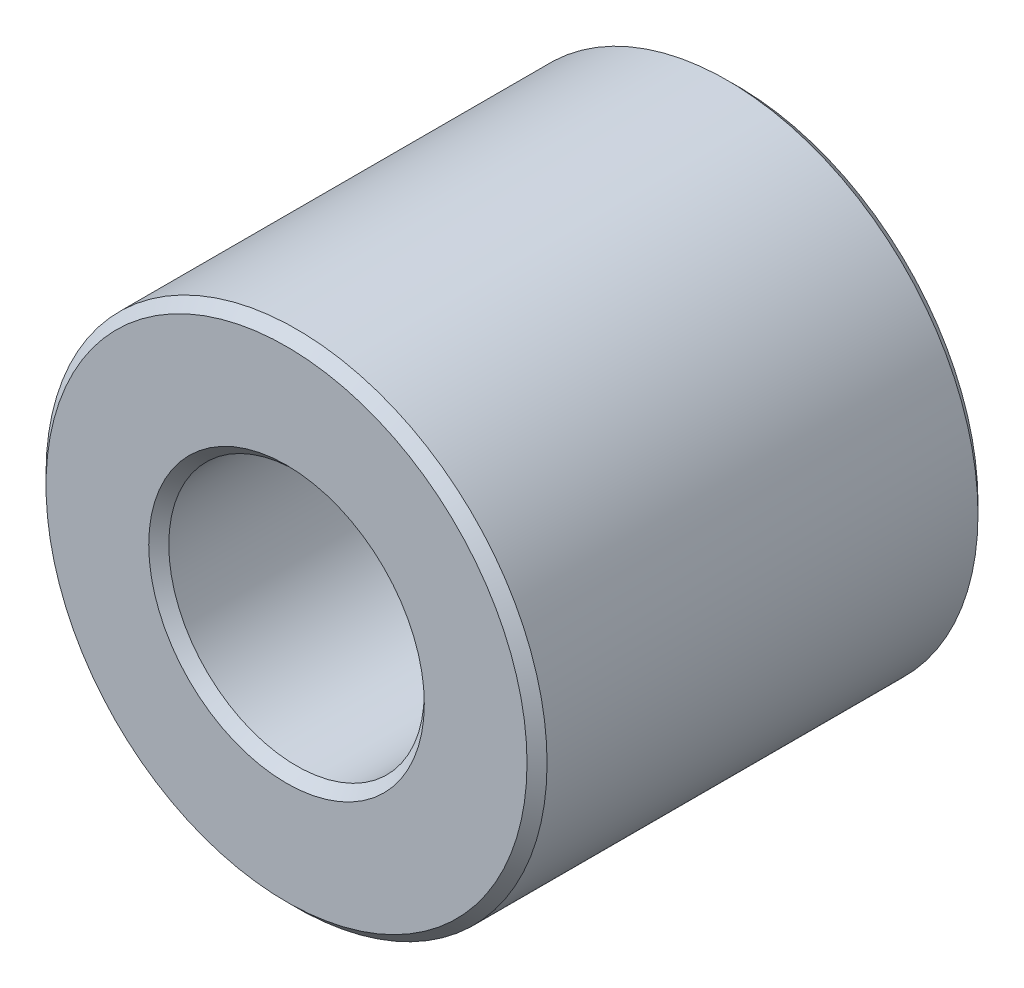
SolidWorks part; units mm, degrees
material "6061-T6 (SS)"
ref_plane "Front Plane" through (0, 0, 0) normal (0, 0, 1) x (1, 0, 0)
ref_plane "Top Plane" through (0, 0, 0) normal (0, 1, 0) x (1, 0, 0)
ref_plane "Right Plane" through (0, 0, 0) normal (1, 0, 0) x (0, 0, -1)
sketch "Sketch1" plane through (0, 0, 0) normal (0, 0, 1) x (1, 0, 0)
  circle A0 centre (0, 0) radius 2.55
  circle A1 centre (0, 0) radius 5
  dimension "D1" = 5.1
  dimension "D2" = 10
extrude "Boss-Extrude1" add sketch "Sketch1" along normal blind 9
chamfer "Chamfer1" distance 0.2 angle 45 4 edges at (5, 0, 0) (2.55, 0, 0) (2.55, 0, 9) (5, 0, 9)
